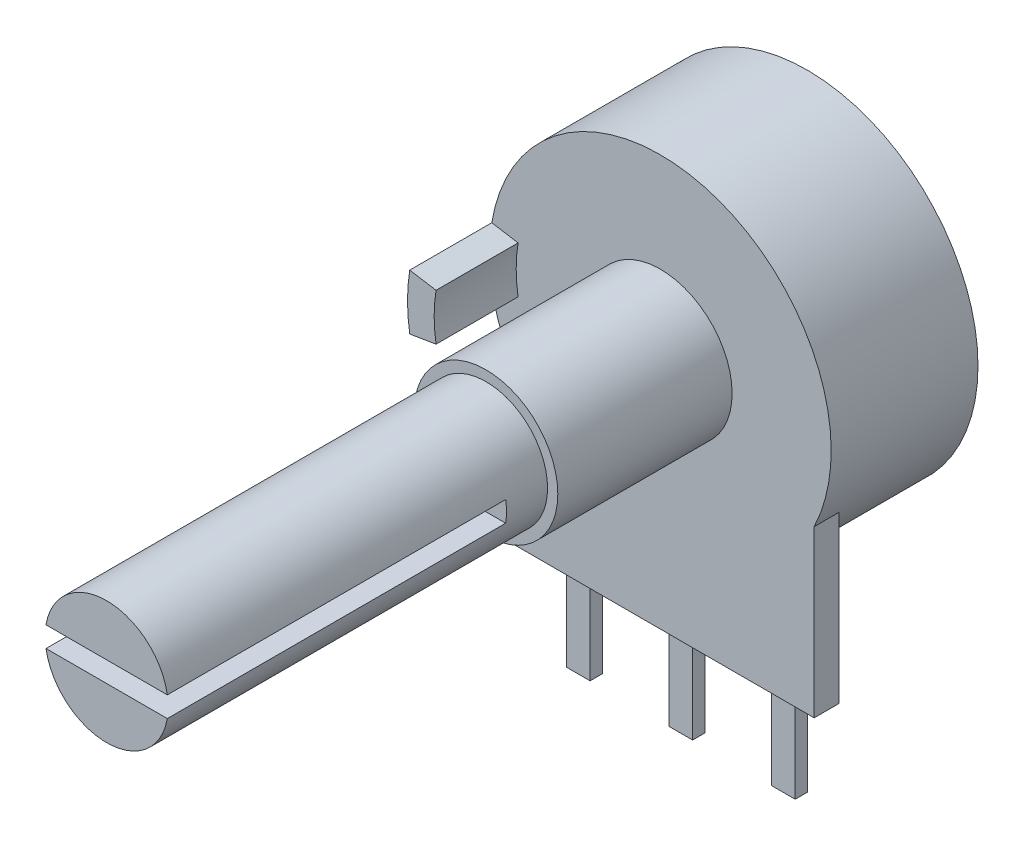
SolidWorks part; units mm, degrees
ref_plane "Front Plane" through (0, 0, 0) normal (0, 0, 1) x (1, 0, 0)
ref_plane "Top Plane" through (0, 0, 0) normal (0, 1, 0) x (1, 0, 0)
ref_plane "Right Plane" through (0, 0, 0) normal (1, 0, 0) x (0, 0, -1)
sketch "Sketch1" plane through (0, 0, 0) normal (0, 0, 1) x (1, 0, 0)
  circle A0 centre (0, 0) radius 8.33
  dimension "D1" = 16.66
extrude "Boss-Extrude1" add sketch "Sketch1" along normal blind 7.16
sketch "Sketch2" plane through (0, 0, 7.16) normal (0, 0, 1) x (1, 0, 0)
  circle A0 centre (0, 0) radius 3.5
  dimension "D1" = 7
extrude "Boss-Extrude2" add sketch "Sketch2" along normal blind 8.5
sketch "Sketch6" plane through (0, 0, 15.66) normal (0, 0, 1) x (1, 0, 0)
  circle A0 centre (0, 0) radius 3
  dimension "D1" = 6
extrude "Boss-Extrude6" add sketch "Sketch6" along normal blind 27 from surface starting at face at (3.5, 0, 7.16)
sketch "Sketch7" plane through (0, 0, 34.16) normal (0, 0, 1) x (1, 0, 0)
  line L0 (-3, 0) -> (3, 0) construction
  line L1 (-3, -0.5) -> (3, -0.5)
  line L2 (-3, -0.5) -> (-3, 0.5)
  line L3 (3, -0.5) -> (3, 0.5)
  line L4 (-3, 0.5) -> (3, 0.5)
  line L5 (3, 0) -> (-3, 0) construction
  line L6 (0, -0.5) -> (0, 0.5) construction
  circle A0 centre (0, 0) radius 3 construction
  circle A1 centre (0, 0) radius 3 construction
  point P8 (0, 0)
  dimension "D1" = 1
extrude "Cut-Extrude1" cut sketch "Sketch7" against normal offset from surface (16.5 mm away) 2 up to face at (3, 0, 15.66)
sketch "Sketch3" plane through (0, 0, 7.16) normal (0, 0, 1) x (1, 0, 0)
  line L1 (-7.5, -11.7) -> (7.5, -11.7)
  line L2 (-7.5, -11.7) -> (-7.5, -0.4955)
  line L3 (-7.5, -0.4955) -> (7.5, -0.4955)
  line L4 (7.5, -11.7) -> (7.5, -0.4955)
  line L5 (0, -0.4955) -> (0, -11.7) construction
  line L6 (-7.5, -6.0977) -> (7.5, -6.0977) construction
  circle A0 centre (0, 0) radius 8.33 construction
  point P0 (0, -6.0977)
  dimension "D1" = 15
  dimension "D2" = 11.7
extrude "Boss-Extrude3" add sketch "Sketch3" against normal blind 1.2
sketch "Sketch4" plane through (0, 0, 5.96) normal (0, 0, -1) x (-1, 0, 0)
  line L0 (0, -8.33) -> (0, -11.7) construction
  line L1 (7.5, -11.7) -> (-7.5, -11.7) construction
  line L2 (-0.575, -11.7) -> (0.575, -11.7)
  line L3 (-0.575, -6.8) -> (0.575, -6.8)
  line L4 (-0.575, -6.8) -> (-0.575, -16.6)
  line L5 (-0.575, -16.6) -> (0.575, -16.6)
  line L6 (0.575, -6.8) -> (0.575, -16.6)
  line L7 (0, -16.6) -> (0, -6.8) construction
  line L8 (-0.575, -11.7) -> (0.575, -11.7) construction
  arc A0 (-7.5, -3.6248) -> (7.5, -3.6248) centre (0, 0) ccw construction
  line M4 (-7.5, -11.7) -> (7.5, -11.7)
  dimension "D1" = 1.15
  dimension "D2" = 4.9
extrude "Boss-Extrude4" add sketch "Sketch4" along normal blind 0.6 from offset 0.2 contours L6 L4 L5 M4 region at (0, -14.15, 5.96) offset against normal yes
pattern_linear "LPattern1" count 2 spacing 5 along (1, 0, 0) count 2 spacing 5 along (-1, 0, 0) of "Boss-Extrude4"
sketch "Sketch5" plane through (0, 0, 7.16) normal (0, 0, 1) x (1, 0, 0)
  line L0 (0, 0) -> (-8.33, 0) construction
  line L1 (-8.2199, 1.35) -> (-6.9371, 1.1393)
  line L2 (-8.2199, -1.35) -> (-6.9371, -1.1393)
  arc A0 (7.5, -3.6248) -> (-7.5, -3.6248) centre (0, 0) ccw construction
  arc A1 (-6.9371, -1.1393) -> (-6.9371, 1.1393) centre (0, 0) cw
  arc A2 (-8.2199, -1.35) -> (-8.2199, 1.35) centre (0, 0) cw
  point P11 (0, 0)
  point P12 (-7.03, 0)
  dimension "D1" = 1.3
  dimension "D2" = 2.7
extrude "Boss-Extrude5" add sketch "Sketch5" along normal blind 4
